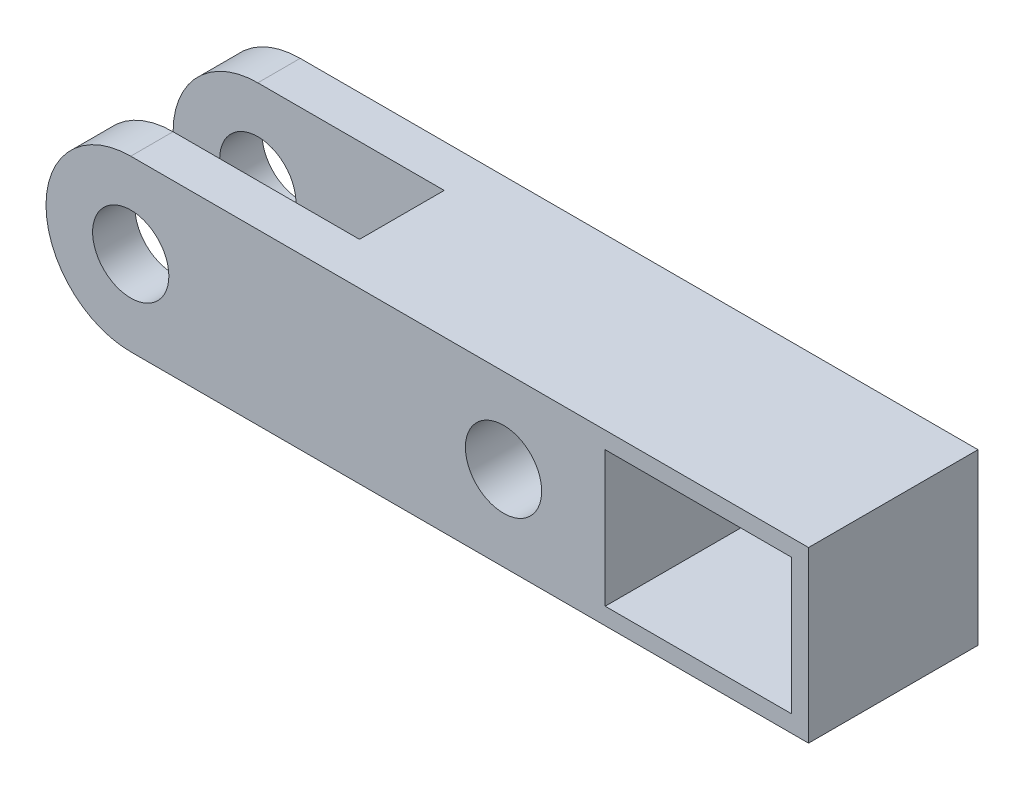
SolidWorks part; units mm, degrees
ref_plane "Front Plane" through (0, 0, 0) normal (0, 0, 1) x (1, 0, 0)
ref_plane "Top Plane" through (0, 0, 0) normal (0, 1, 0) x (1, 0, 0)
ref_plane "Right Plane" through (0, 0, 0) normal (1, 0, 0) x (0, 0, -1)
sketch "Sketch1" plane through (0, 0, 0) normal (0, 0, 1) x (1, 0, 0)
  line L1 (0, 5) -> (40, 5)
  line L2 (0, -5) -> (40, -5)
  line L3 (40, 5) -> (40, -5)
  arc A0 (0, 5) -> (0, -5) centre (0, 0) ccw
  circle A2 centre (0, 0) radius 2.25
  point P1 (0, 0)
  point P3 (0, 0)
  dimension "D1" = 5
  dimension "D3" = 4.5
  dimension "D2" = 40
  dimension "D4" = 10
extrude "Boss-Extrude1" add sketch "Sketch1" along normal mid plane 10
sketch "Sketch2" plane through (0, -5, 5) normal (0, 0, -1) x (1, 0, 0)
  line L3 (40, 0) -> (40, -10) construction
  circle A0 centre (22, -5) radius 2.25
  point P3 (0, 0)
  point P4 (0, 0)
  point P8 (15, -6.0639)
  dimension "D1" = 4.5
  dimension "D2" = 18
extrude "Cut-Extrude2" cut sketch "Sketch2" along normal through all
sketch "Sketch4" plane through (0, 0, 5) normal (0, 0, -1) x (-1, 0, 0)
  line L1 (-28, -4) -> (-39, -4)
  line L2 (-28, -4) -> (-28, 4)
  line L3 (-28, 4) -> (-39, 4)
  line L4 (-39, -4) -> (-39, 4)
  line L6 (-40, 5) -> (0, 5) construction
  line L8 (-40, -5) -> (-40, 5) construction
  point P4 (-25.9891, -5)
  dimension "D1" = 8
  dimension "D2" = 11
  dimension "D3" = 1
  dimension "D4" = 1
extrude "Cut-Extrude5" cut sketch "Sketch4" along normal through all
sketch "Sketch5" plane through (0, -5, 0) normal (0, -1, 0) x (1, 0, 0)
  line L0 (-5, 5) -> (-5, -5) construction
  line L1 (-5, -2.5) -> (11, -2.5)
  line L2 (-5, -2.5) -> (-5, 2.5)
  line L3 (-5, 2.5) -> (11, 2.5)
  line L4 (11, -2.5) -> (11, 2.5)
  line L5 (40, 5) -> (40, -5) construction
  point P8 (40, 0)
  point P9 (11, 0)
  dimension "D1" = 16
  dimension "D2" = 5
extrude "Cut-Extrude6" cut sketch "Sketch5" against normal through all
